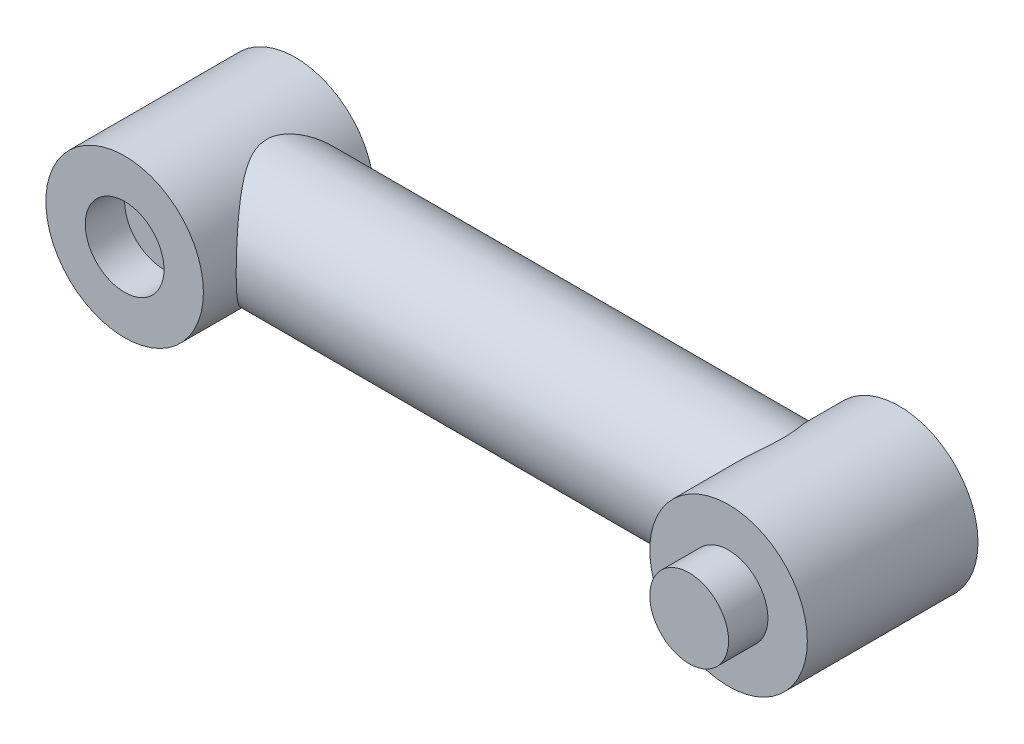
SolidWorks part; units mm, degrees
material "1060 Alloy"
ref_plane "Front Plane" through (0, 0, 0) normal (0, 0, 1) x (1, 0, 0)
ref_plane "Top Plane" through (0, 0, 0) normal (0, 1, 0) x (1, 0, 0)
ref_plane "Right Plane" through (0, 0, 0) normal (1, 0, 0) x (0, 0, -1)
sketch "Sketch1" plane through (0, 0, 0) normal (0, 0, 1) x (1, 0, 0)
  line L0 (213.4169, 0) -> (16.5831, 0) construction
  line L1 (16.5831, 25) -> (213.4169, 25)
  line L2 (16.5831, 25) -> (16.5831, -25)
  line L3 (16.5831, -25) -> (213.4169, -25)
  line L4 (213.4169, 25) -> (213.4169, -25)
  circle A0 centre (0, 0) radius 30
  circle A1 centre (0, 0) radius 15
  circle A2 centre (230, 0) radius 30
  circle A3 centre (230, 0) radius 15
  point P7 (16.5831, 0)
  dimension "D1" = 60
  dimension "D2" = 30
  dimension "D3" = 60
  dimension "D4" = 30
  dimension "D5" = 230
  dimension "D6" = 50
extrude "Boss-Extrude1" add sketch "Sketch1" along normal mid plane 65 from offset 5 contours L2 A0 A1 | L4 A2 A3 | A3 | A1 | A0 L0 L2 | L0 A0 L2 | L0 L4 A2 | L4 L0 A2 region at (22.0682, -9.7354, 0) region at (22.0682, 9.7354, 0) region at (15.8235, -12.5, 0) region at (207.9318, 9.7354, 0) region at (207.9318, -9.7354, 0) region at (214.1765, 12.5, 0) region at (0, 0, 0) region at (230, 0, 0)
revolve "Revolve1" add sketch "Sketch1<3>" angle 360 about L0 region at (115, 12.7933, 0)
sketch "Sketch1<3>" plane through (0, 0, 0) normal (0, 0, 1) x (1, 0, 0) same geometry as "Sketch1"
extrude "Cut-Extrude1" cut sketch "Sketch1<4>" against normal blind 15 from surface contours A1 region at (0, 0, 0) starting at face at (30, 0, 37.5)
sketch "Sketch1<4>" plane through (0, 0, 0) normal (0, 0, 1) x (1, 0, 0) same geometry as "Sketch1"
extrude "Boss-Extrude2" add sketch "Sketch1<5>" along normal blind 15 from surface contours A3 region at (230, 0, 0) starting at face at (15, 0, 37.5)
sketch "Sketch1<5>" plane through (0, 0, 0) normal (0, 0, 1) x (1, 0, 0) same geometry as "Sketch1"
sketch "Sketch2" plane through (0, 0, -27.5) normal (0, 0, -1) x (-1, 0, 0)
  line L0 (0, 0) -> (-230, 0)
